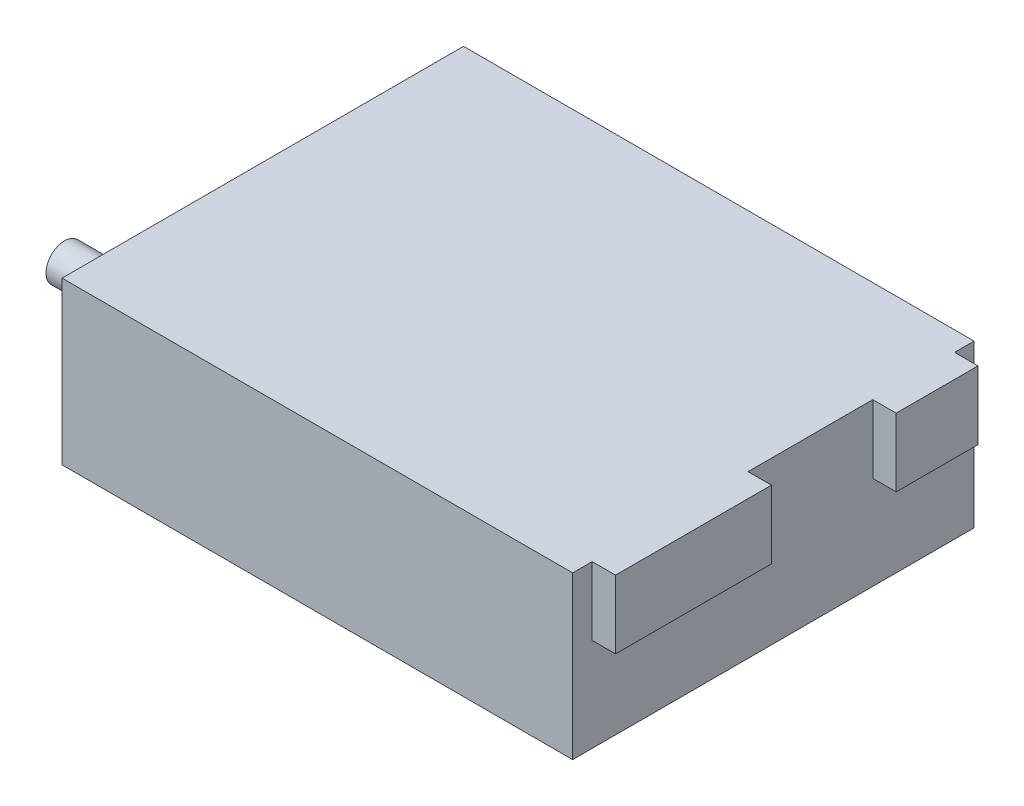
SolidWorks part; units mm, degrees
ref_plane "Front Plane" through (0, 0, 0) normal (0, 0, 1) x (1, 0, 0)
ref_plane "Top Plane" through (0, 0, 0) normal (0, 1, 0) x (1, 0, 0)
ref_plane "Right Plane" through (0, 0, 0) normal (1, 0, 0) x (0, 0, -1)
sketch "Sketch1" plane through (0, 0, 0) normal (0, 1, 0) x (1, 0, 0)
  line L1 (-13.1, 10.3) -> (13.1, 10.3)
  line L2 (-13.1, 10.3) -> (-13.1, -10.3)
  line L3 (-13.1, -10.3) -> (13.1, -10.3)
  line L4 (13.1, 10.3) -> (13.1, -10.3)
  line L5 (-13.1, 10.3) -> (13.1, -10.3) construction
  line L6 (-13.1, -10.3) -> (13.1, 10.3) construction
  point P0 (0, 0)
  dimension "D1" = 26.2
  dimension "D2" = 20.6
extrude "Boss-Extrude1" add sketch "Sketch1" along normal blind 8.3
sketch "Sketch2" plane through (13.1, 0, 0) normal (1, 0, 0) x (0, 0, -1)
  line L0 (-10.3, 8.3) -> (10.3, 8.3) construction
  line L1 (-9.3, 8.3) -> (-1.3, 8.3)
  line L2 (-9.3, 8.3) -> (-9.3, 4.8)
  line L3 (-9.3, 4.8) -> (-1.3, 4.8)
  line L4 (-1.3, 8.3) -> (-1.3, 4.8)
  line L5 (-10.3, 8.3) -> (-10.3, 0) construction
  line L6 (10.3, 8.3) -> (10.3, 0) construction
  line L7 (9.3, 8.3) -> (5.1, 8.3)
  line L8 (9.3, 8.3) -> (9.3, 4.8)
  line L9 (9.3, 4.8) -> (5.1, 4.8)
  line L10 (5.1, 8.3) -> (5.1, 4.8)
  dimension "D1" = 8
  dimension "D2" = 3.5
  dimension "D3" = 1
  dimension "D4" = 4.2
  dimension "D5" = 1
extrude "Boss-Extrude2" add sketch "Sketch2" along normal blind 1.2
sketch "Sketch3" plane through (-13.1, 0, 0) normal (-1, 0, 0) x (0, 0, 1)
  circle A0 centre (5.1748, 3.9453) radius 0.95
  dimension "D1" = 1.9
extrude "Boss-Extrude3" add sketch "Sketch3" along normal blind 5
